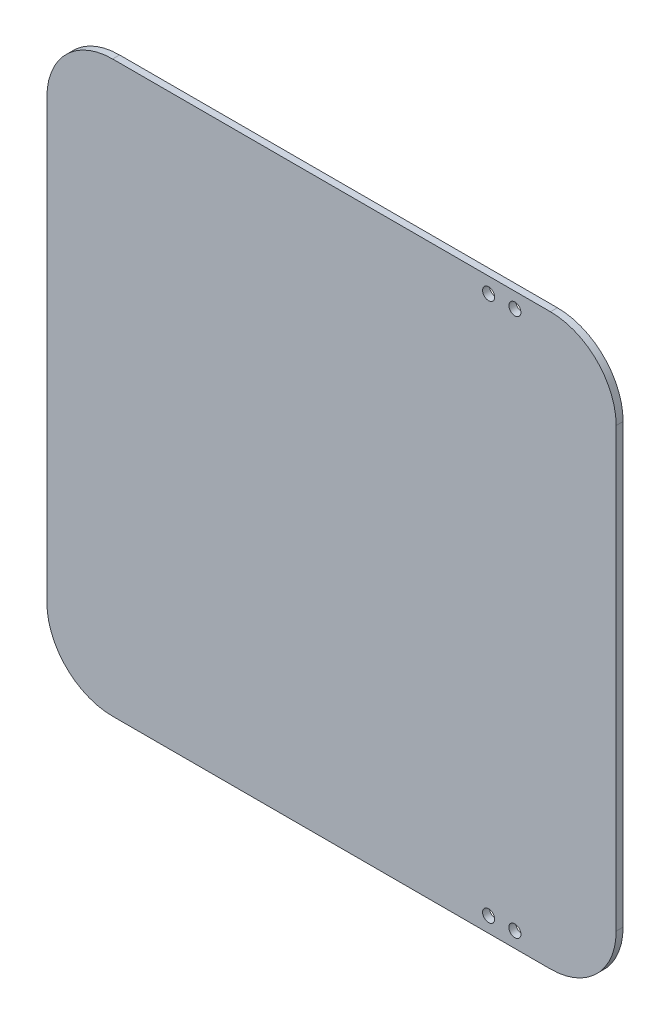
SolidWorks part; units mm, degrees
ref_plane "Front Plane" through (0, 0, 0) normal (0, 0, 1) x (1, 0, 0)
ref_plane "Top Plane" through (0, 0, 0) normal (0, 1, 0) x (1, 0, 0)
ref_plane "Right Plane" through (0, 0, 0) normal (1, 0, 0) x (0, 0, -1)
sketch "Sketch1" plane through (0, 0, 0) normal (0, 0, 1) x (1, 0, 0)
  line L4 (79.7168, 314.2679) -> (-120.2832, 314.2679)
  line L5 (109.7168, 84.2679) -> (109.7168, 284.2679)
  line L6 (-120.2832, 54.2679) -> (79.7168, 54.2679)
  line L7 (-150.2832, 284.2679) -> (-150.2832, 84.2679)
  arc A4 (-120.2832, 314.2679) -> (-150.2832, 284.2679) centre (-120.2832, 284.2679) ccw
  arc A5 (109.7168, 284.2679) -> (79.7168, 314.2679) centre (79.7168, 284.2679) ccw
  arc A6 (79.7168, 54.2679) -> (109.7168, 84.2679) centre (79.7168, 84.2679) ccw
  arc A7 (-150.2832, 84.2679) -> (-120.2832, 54.2679) centre (-120.2832, 84.2679) ccw
extrude "Boss-Extrude1" add sketch "Sketch1" against normal blind 3.175 contours L4 A4 L7 A7 L6 A6 L5 A5
sketch "Sketch2" plane through (0, 0, 0) normal (0, 0, 1) x (1, 0, 0)
  circle A0 centre (51.4668, 307.2679) radius 2.75 construction
  circle A1 centre (63.4668, 307.2679) radius 2.75 construction
  circle A2 centre (51.4668, 307.2679) radius 2.75
  circle A3 centre (63.4668, 307.2679) radius 2.75
  circle A4 centre (63.4668, 61.2679) radius 2.75 construction
  circle A5 centre (51.4668, 61.2679) radius 2.75 construction
  circle A6 centre (63.4668, 61.2679) radius 2.75
  circle A7 centre (51.4668, 61.2679) radius 2.75
extrude "Cut-Extrude1" cut sketch "Sketch2" against normal through all
